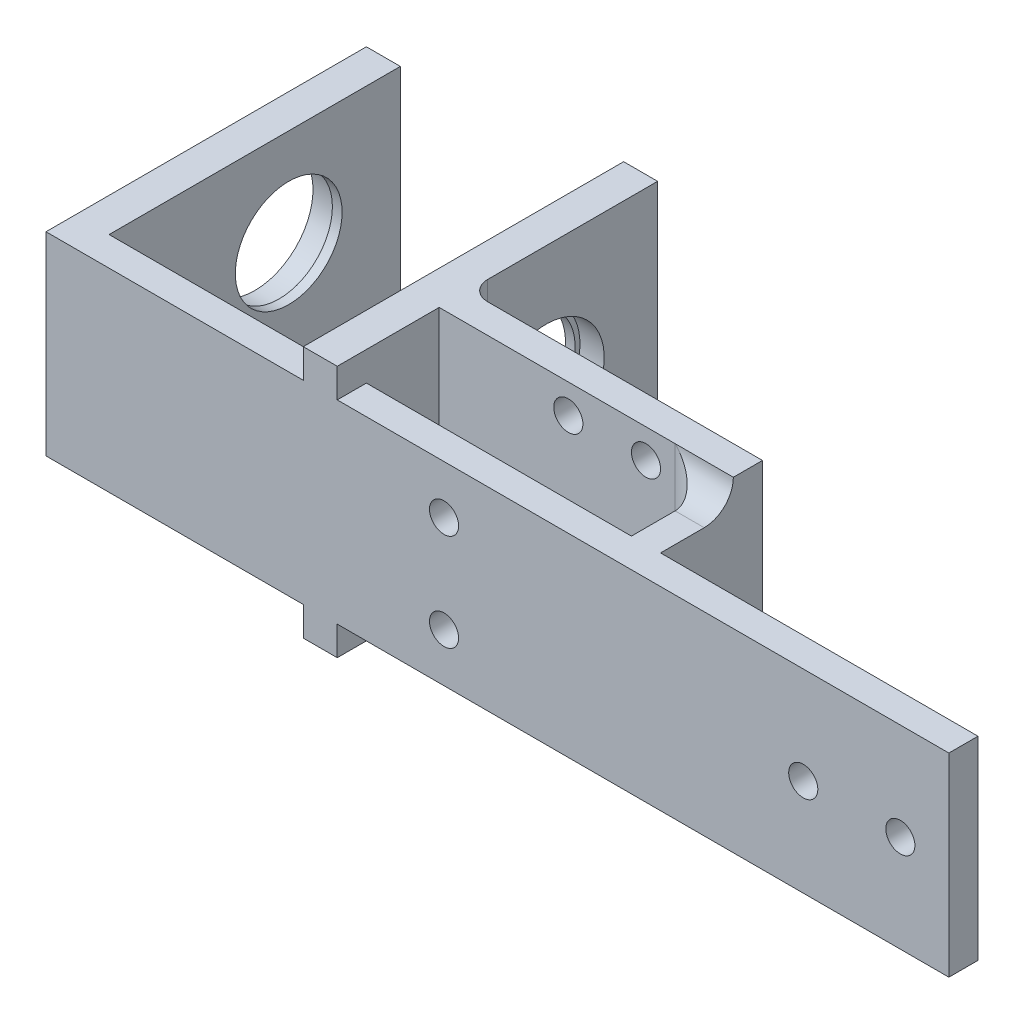
SolidWorks part; units mm, degrees
ref_plane "前视基准面" through (0, 0, 0) normal (0, 0, 1) x (1, 0, 0)
ref_plane "上视基准面" through (0, 0, 0) normal (0, 1, 0) x (1, 0, 0)
ref_plane "右视基准面" through (0, 0, 0) normal (1, 0, 0) x (0, 0, -1)
sketch "草图1" plane through (0, 0, 0) normal (0, 0, 1) x (1, 0, 0)
  line L0 (-10, 9.8542) -> (10, 9.8542)
  line L1 (-10, 9.8542) -> (-10, -10.1458)
  line L2 (10, 9.8542) -> (10, -10.1458)
  line L3 (-10, 9.8542) -> (-53, 9.8542)
  line L4 (-10, -0.1458) -> (10, -0.1458) construction
  line L5 (0, 9.8542) -> (0, -9.8542) construction
  line L6 (-53, -0.1458) -> (-53, 12.8542)
  line L7 (-53, -10.1458) -> (-10, -10.1458)
  line L8 (-53, -0.1458) -> (-53, -13.1458)
  line L9 (-53, -13.1458) -> (-56.5, -13.1458)
  line L10 (-56.5, 12.8542) -> (-56.5, 9.8542)
  line L11 (-53, 12.8542) -> (-56.5, 12.8542)
  line L12 (-56.5, 9.8542) -> (-79.5, 9.8542)
  line L13 (-10, -10.1458) -> (10, -10.1458)
  line L14 (-79.5, -10.1458) -> (-56.5, -10.1458)
  line L15 (-79.5, 9.8542) -> (-79.5, -10.1458)
  line L16 (-79.5, -10.1458) -> (-83, -10.1458)
  line L17 (-83, -10.1458) -> (-83, 9.8542)
  line L18 (-83, 9.8542) -> (-79.5, 9.8542)
  line L19 (-56.5, -10.1458) -> (-56.5, -13.1458)
  line L20 (-56.5, 9.8542) -> (-56.5, -10.1458)
  circle A2 centre (-5, -0.1458) radius 1.5
  circle A3 centre (5, -0.1458) radius 1.5
extrude "凸台-拉伸1" add sketch "草图1" along normal blind 3 contours L6 L8 L7 L1 L3 | L1 L13 L2 L0 | L6 L11 L9 L8 | L12 L14 | L18 L17 L16 region at (0, -0.1458, 0) region at (-31.5, -0.1458, 0) region at (-54.75, -0.1458, 0) region at (-68, -0.1458, 0) region at (-81.25, -0.1458, 0)
extrude "凸台-拉伸2" add sketch "草图1<3>" against normal blind 30 contours L10 L20 L19 L9 L8 L6 L11
sketch "草图1<3>" plane through (0, 0, 0) normal (0, 0, 1) x (1, 0, 0) same geometry as "草图1"
extrude "凸台-拉伸3" add sketch "草图1<4>" against normal blind 30 contours L18 L17 L16 region at (-81.25, -0.1458, 0)
sketch "草图1<4>" plane through (0, 0, 0) normal (0, 0, 1) x (1, 0, 0) same geometry as "草图1"
sketch "草图3" plane through (-83, 0, 0) normal (-1, 0, 0) x (0, 0, 1)
  circle A0 centre (-18.5, -0.1458) radius 6
extrude "切除-拉伸2" cut sketch "草图3" against normal blind 38 contours A0 region at (-83, -0.1458, -18.5)
sketch "草图4" plane through (-56.5, 0, 0) normal (-1, 0, 0) x (0, 0, 1)
  circle A0 centre (-18.5, -0.1458) radius 6
  circle A1 centre (-18.5, -0.1458) radius 5.5
extrude "凸台-拉伸4" add sketch "草图4" against normal blind 1
ref_plane "基准面1" through (-68, 0, 0) normal (1, 0, 0) x (0, 0, -1)
sketch "草图5" plane through (-79.5, 0, 0) normal (1, 0, 0) x (0, 0, -1)
  circle A0 centre (18.5, -0.1458) radius 6
  circle A1 centre (18.5, -0.1458) radius 5.5
extrude "凸台-拉伸5" add sketch "草图5" against normal blind 1
sketch "草图7" plane through (0, 0, 3) normal (0, 0, 1) x (1, 0, 0)
  line L0 (-49.5, -10.1461) -> (-49.5, 10.8539)
  line L1 (-34.5, -10.1461) -> (-34.5, 10.8539)
  line L2 (-49.5, 10.8539) -> (-34.5, 10.8539)
  line L3 (-49.5, -10.1461) -> (-34.5, -10.1461)
  line L31 (10, -10.1461) -> (10, 9.8539)
  circle A4 centre (-42, -5.1461) radius 1.5
  circle A6 centre (-42, 4.8539) radius 1.5
extrude "切除-拉伸4" cut sketch "草图7" against normal blind 5 contours A6 | A4 region at (-42, -5.1461, 3) region at (-42, 4.8539, 3)
sketch "草图9" plane through (-53, 0, 0) normal (1, 0, 0) x (0, 0, -1)
  line L1 (10.5, 12.8542) -> (10.5, -13.1458)
  line L2 (10.5, -13.1458) -> (7.5, -13.1458)
  line L3 (7.5, -13.1458) -> (7.5, 12.8542)
  line L4 (7.5, 12.8542) -> (10.5, 12.8542)
extrude "凸台-拉伸6" add sketch "草图9" along normal blind 30.3
sketch "草图10" plane through (0, 0, -7.5) normal (0, 0, 1) x (1, 0, 0)
  circle A0 centre (-31.6991, 9.8548) radius 1.5
  circle A1 centre (-39.6991, 9.855) radius 1.5
  circle A2 centre (-31.6994, -10.1466) radius 1.5
  circle A4 centre (-39.6994, -10.1466) radius 1.5
extrude "切除-拉伸6" cut sketch "草图10" against normal blind 10
sketch "草图11" plane through (0, -13.1458, 0) normal (0, -1, 0) x (1, 0, 0)
  line L0 (-53, -10.5) -> (-53, -24.5)
  line L1 (-53, -10.5) -> (-41, -10.5)
  line L2 (-41, -10.5) -> (-53, -24.5)
ref_plane "基准面2" through (0, -0.1458, 0) normal (0, 1, 0) x (1, 0, 0)
fillet "圆角2" radius 2 1 edges at (-53, -0.1458, -10.5)
sketch "草图13" plane through (0, 0, -10.5) normal (0, 0, -1) x (-1, 0, 0)
  line L0 (25.7, 9.8542) -> (25.7, -10.1458)
  line L1 (25.7, -10.1458) -> (22.7, -10.1458)
  line L2 (22.7, -10.1458) -> (22.7, 9.8542)
  line L3 (22.7, 9.8542) -> (25.7, 9.8542)
extrude "凸台-拉伸8" add sketch "草图13" against normal up to surface (10.5 mm away) up to face at (-68, -0.1458, 0)
fillet "圆角5" radius 3 3 edges at (-24.2, 9.8542, -7.5) (-25.7, -0.1458, -7.5) (-24.2, -10.1458, -7.5)
